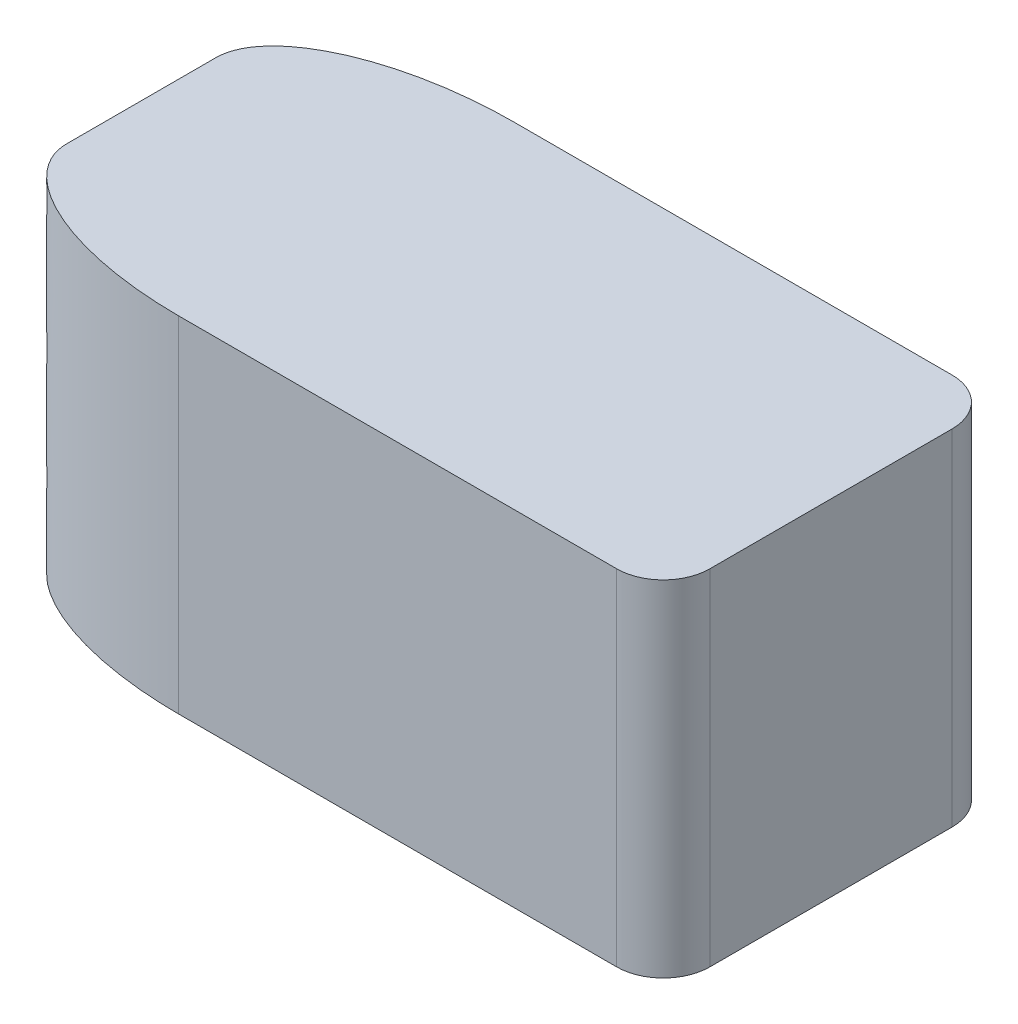
SolidWorks part; units mm, degrees
ref_plane "Front Plane" through (0, 0, 0) normal (0, 0, 1) x (1, 0, 0)
ref_plane "Top Plane" through (0, 0, 0) normal (0, 1, 0) x (1, 0, 0)
ref_plane "Right Plane" through (0, 0, 0) normal (1, 0, 0) x (0, 0, -1)
sketch "Sketch1" plane through (0, 0, 0) normal (0, 1, 0) x (1, 0, 0)
  line L1 (37, -18) -> (-37, -18)
  line L2 (37, -18) -> (37, 18)
  line L3 (37, 18) -> (-37, 18)
  line L4 (-37, -18) -> (-37, 18)
  line L5 (37, -18) -> (-37, 18) construction
  line L6 (37, 18) -> (-37, -18) construction
  point P0 (0, 0)
  dimension "D1" = 36
  dimension "D2" = 74
extrude "Boss-Extrude1" add sketch "Sketch1" along normal mid plane 37
fillet "Fillet1" radius 10 2 edges at (-37, 0, -18) (-37, 0, 18) second distance 22 first distance on face at (-37, 0, 0)
fillet "Fillet2" radius 5 2 edges at (37, 0, -18) (37, 0, 18)
